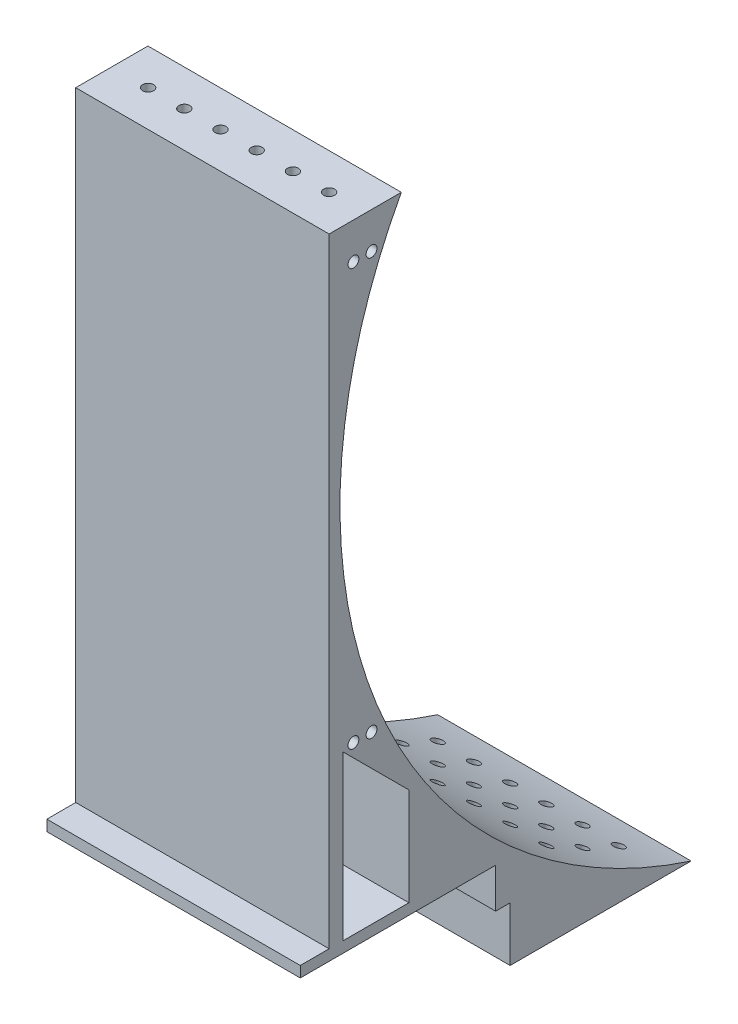
SolidWorks part; units mm, degrees
ref_plane "Front Plane" through (0, 0, 0) normal (0, 0, 1) x (1, 0, 0)
ref_plane "Top Plane" through (0, 0, 0) normal (0, 1, 0) x (1, 0, 0)
ref_plane "Right Plane" through (0, 0, 0) normal (1, 0, 0) x (0, 0, -1)
sketch "Sketch1" plane through (0, 0, 0) normal (1, 0, 0) x (0, 0, -1)
  line L0 (0, 200) -> (0, 0)
  line L1 (0, 0) -> (100, 0)
  line L2 (0, 200) -> (19.9466, 200)
  arc A0 (19.9466, 200) -> (100, 0) centre (143, 133.2329) ccw
  dimension "D1" = 140
  dimension "D4" = 143
  dimension "D2" = 200
  dimension "D3" = 133.2329
extrude "Boss-Extrude1" add sketch "Sketch1" along normal blind 70
ref_plane "Plane1" through (0, 0, -100) normal (0, 0, 1) x (1, 0, 0)
sketch "Sketch5" plane through (70, 0, 0) normal (1, 0, 0) x (0, 0, -1)
  line L0 (22.0273, 26) -> (22.0273, 56)
  line L1 (0, 0) -> (50, 0)
  line L3 (22.0273, 26) -> (46, 26)
  line L4 (50, 0) -> (50, 15)
  line L5 (22.0273, 56) -> (3.8589, 74.1684)
  line L7 (0, 26) -> (0, 0)
  line L8 (3.8589, 74.1684) -> (3.8589, 26)
  line L11 (50, 15) -> (46, 15)
  line L12 (46, 26) -> (46, 15)
  line L13 (3.8589, 26) -> (0, 26)
  dimension "D1" = 135
  dimension "D2" = 50
  dimension "D3" = 15
  dimension "D4" = 30
  dimension "D5" = 4
  dimension "D6" = 11
extrude "Cut-Extrude2" cut sketch "Sketch5" against normal through all
sketch "Sketch6" plane through (0, 0, -22.0273) normal (0, 0, 1) x (1, 0, 0)
  line L0 (70, 26) -> (70, 56) construction
  line L1 (0, 26) -> (70, 26)
  line L2 (0, 26) -> (0, 29)
  line L3 (0, 29) -> (70, 29)
  line L4 (70, 26) -> (70, 29)
  dimension "D1" = 3
extrude "Boss-Extrude2" add sketch "Sketch6" along normal blind 30
sketch "Sketch7" plane through (0, 200, 0) normal (0, 1, 0) x (1, 0, 0)
  line L1 (0, 19.9466) -> (0, 0) construction
  line L2 (70, 0) -> (0, 0) construction
  circle A0 centre (10, 10) radius 1.5
  circle A1 centre (20, 10) radius 1.5
  circle A2 centre (30, 10) radius 1.5
  circle A3 centre (40, 10) radius 1.5
  circle A4 centre (50, 10) radius 1.5
  circle A5 centre (60, 10) radius 1.5
  dimension "D2" = 3
  dimension "D3" = 10
  dimension "D1" = 10
  dimension "D4" = 6
extrude "Cut-Extrude3" cut sketch "Sketch7" against normal blind 17
sketch "Sketch8" plane through (0, 0, 0) normal (0, -1, 0) x (1, 0, 0)
  line L0 (70, -100) -> (0, -100) construction
  line L1 (0, -50) -> (0, -100) construction
  circle A0 centre (10, -90) radius 1.5
  circle A1 centre (20, -90) radius 1.5
  circle A2 centre (30, -90) radius 1.5
  circle A3 centre (40, -90) radius 1.5
  circle A4 centre (50, -90) radius 1.5
  circle A5 centre (60, -90) radius 1.5
  circle A6 centre (20, -80) radius 1.5
  circle A7 centre (30, -80) radius 1.5
  circle A8 centre (40, -80) radius 1.5
  circle A9 centre (50, -80) radius 1.5
  circle A10 centre (60, -80) radius 1.5
  circle A11 centre (20, -70) radius 1.5
  circle A12 centre (30, -70) radius 1.5
  circle A13 centre (40, -70) radius 1.5
  circle A14 centre (50, -70) radius 1.5
  circle A15 centre (60, -70) radius 1.5
  circle A16 centre (20, -60) radius 1.5
  circle A17 centre (30, -60) radius 1.5
  circle A18 centre (40, -60) radius 1.5
  circle A19 centre (50, -60) radius 1.5
  circle A20 centre (60, -60) radius 1.5
  circle A21 centre (10, -80) radius 1.5
  circle A22 centre (10, -70) radius 1.5
  circle A23 centre (10, -60) radius 1.5
  dimension "D1" = 3
  dimension "D2" = 10
  dimension "D3" = 10
  dimension "D4" = 6
  dimension "D5" = 4
extrude "Cut-Extrude4" cut sketch "Sketch8" against normal blind 15
sketch "Sketch9" plane through (0, 26, 0) normal (0, -1, 0) x (1, 0, 0)
  line L0 (35, 7.9727) -> (35, -46) construction
  line L1 (0, 7.9727) -> (70, 7.9727) construction
  line L2 (0, -46) -> (70, -46) construction
  line L3 (0, -46) -> (70, -46) construction
  circle A0 centre (20, -6) radius 1.5
  circle A1 centre (20, -31) radius 1.5
  circle A2 centre (50, -31) radius 1.5
  circle A3 centre (50, -6) radius 1.5
  dimension "D1" = 3
  dimension "D2" = 3
  dimension "D3" = 25
  dimension "D4" = 15
  dimension "D5" = 15
extrude "Cut-Extrude5" cut sketch "Sketch9" against normal blind 20
sketch "Sketch10" plane through (70, 0, 0) normal (1, 0, 0) x (0, 0, -1)
  line L0 (46, 26) -> (-7.9727, 26) construction
  line L1 (0, 200) -> (0, 29) construction
  circle A0 centre (6.71, 75) radius 1.5
  circle A2 centre (11.71, 75) radius 1.5
  circle A3 centre (6.71, 190) radius 1.5
  circle A4 centre (11.71, 190) radius 1.5
  dimension "D2" = 3
  dimension "D3" = 6.71
  dimension "D6" = 5
  dimension "D7" = 115
  dimension "D1" = 49
  dimension "D4" = 2
  dimension "D5" = 2
extrude "Cut-Extrude6" cut sketch "Sketch10" against normal through all
